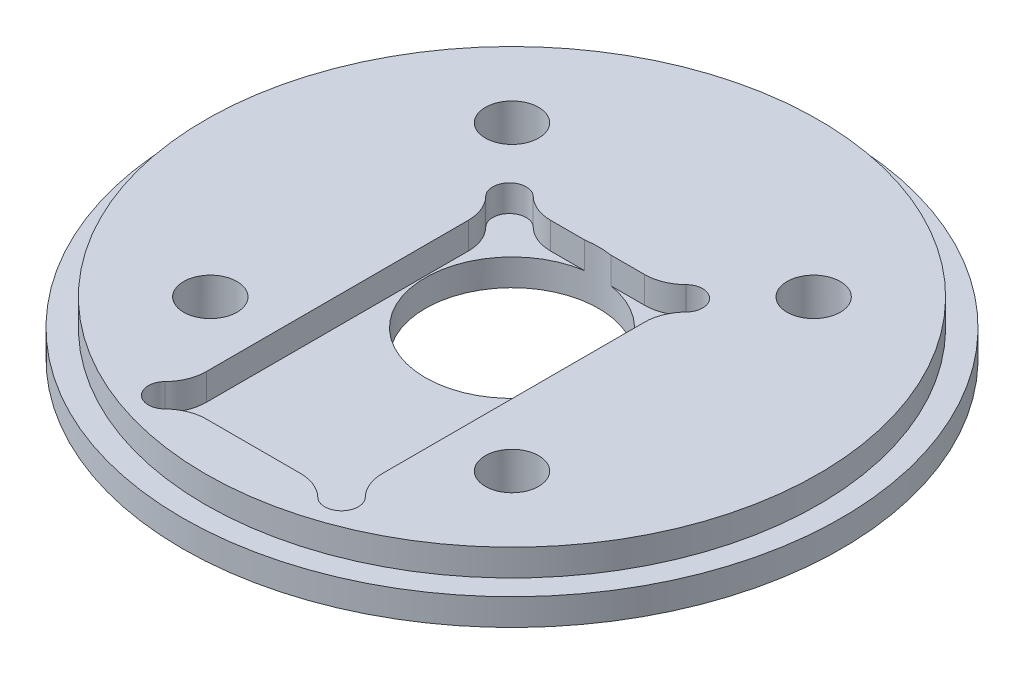
SolidWorks part; units mm, degrees
ref_plane "Front Plane" through (0, 0, 0) normal (0, 0, 1) x (1, 0, 0)
ref_plane "Top Plane" through (0, 0, 0) normal (0, 1, 0) x (1, 0, 0)
ref_plane "Right Plane" through (0, 0, 0) normal (1, 0, 0) x (0, 0, -1)
sketch "Sketch2" plane through (0, 0, 0) normal (0, 1, 0) x (1, 0, 0)
  circle A0 centre (0, 0) radius 39.243
  dimension "D1" = 78.486
extrude "Boss-Extrude1" add sketch "Sketch2" along normal blind 6.35
sketch "Sketch4" plane through (0, 6.35, 0) normal (0, 1, 0) x (1, 0, 0)
  circle A0 centre (0, 0) radius 36.5125
  circle A1 centre (0, 0) radius 39.243 construction
  circle A2 centre (0, 0) radius 39.243
  dimension "D1" = 73.025
extrude "Cut-Extrude1" cut sketch "Sketch4" against normal blind 3.175
sketch "Sketch5" plane through (0, 6.35, 0) normal (0, 1, 0) x (1, 0, 0)
  line L0 (17.9605, 17.9605) -> (-17.9605, -17.9605) construction
  line L1 (-17.9605, 17.9605) -> (17.9605, -17.9605) construction
  line L2 (-1000, 0) -> (49000, 0) construction
  point P1 (-17.9605, -17.9605)
  point P2 (17.9605, 17.9605)
  point P5 (17.9605, -17.9605)
  point P6 (-17.9605, 17.9605)
  dimension "D1" = 50.8
  dimension "D2" = 45
hole_wizard "1/4 (0.25) Diameter Hole1" positions "Sketch5" profile "Sketch6" hole size "1/4" standard "ANSI Inch" end condition through all
sketch "Sketch6" plane through (-17.9605, 6.35, -17.9605) normal (1, 0, 0) x (0, 0, 1)
  line L0 (0, 0) -> (0, 6.35)
  line L1 (0, 6.35) -> (3.175, 6.35)
  line L2 (3.175, 6.35) -> (3.175, 0)
  line L5 (3.175, 0) -> (0, 0)
  line L11 (0, -6.35) -> (0, 107.95) construction
  dimension "Thru Hole Dia." = 6.35
  dimension "Thru Hole Depth" = 6.35
sketch "Sketch7" plane through (0, 6.35, 0) normal (0, 1, 0) x (1, 0, 0)
  point P0 (0, 0)
hole_wizard "13/16 (0.8125) Diameter Hole1" positions "Sketch7" profile "Sketch8" hole size "13/16" standard "ANSI Inch" end condition through all
sketch "Sketch8" plane through (0, 6.35, 0) normal (1, 0, 0) x (0, 0, 1)
  line L0 (0, 0) -> (0, 6.35)
  line L1 (0, 6.35) -> (10.3187, 6.35)
  line L2 (10.3187, 6.35) -> (10.3187, 0)
  line L5 (10.3187, 0) -> (0, 0)
  line L11 (0, -6.35) -> (0, 107.95) construction
  dimension "Thru Hole Dia." = 20.6375
  dimension "Thru Hole Depth" = 6.35
sketch "Sketch11" plane through (0, 6.35, 0) normal (0, 1, 0) x (1, 0, 0)
  line L0 (0, -3.4925) -> (0, 3.4925) construction
  line L1 (-5.601, 10.2) -> (5.601, 10.2)
  line L2 (-10.5, 5.301) -> (-10.5, -25.901)
  line L3 (-5.601, -30.8) -> (5.601, -30.8)
  line L4 (10.5, 5.301) -> (10.5, -25.901)
  line L5 (-10.5, 10.2) -> (10.5, -30.8) construction
  line L6 (-10.5, -30.8) -> (10.5, 10.2) construction
  line L7 (0, -10.3) -> (7.6415, -10.3) construction
  line L8 (-10.5, -30.8) -> (-8.5, -30.8) construction
  line L9 (-10.5, -28.8) -> (-10.5, -30.8) construction
  line L10 (-10.5, 10.2) -> (-8.5, 10.2) construction
  line L11 (-10.5, 10.2) -> (-10.5, 8.2) construction
  line L12 (8.5, -30.8) -> (10.5, -30.8) construction
  line L13 (10.5, -28.8) -> (10.5, -30.8) construction
  line L14 (8.5, 10.2) -> (10.5, 10.2) construction
  line L15 (10.5, 10.2) -> (10.5, 8.2) construction
  arc A0 (-11.9286, -29.4003) -> (-9.1003, -32.2286) centre (-10.5, -30.8) ccw
  arc A1 (11.9286, -29.4003) -> (9.1003, -32.2286) centre (10.5, -30.8) cw
  arc A2 (11.9286, 8.8003) -> (9.1003, 11.6286) centre (10.5, 10.2) ccw
  arc A3 (-11.9286, 8.8003) -> (-9.1003, 11.6286) centre (-10.5, 10.2) cw
  arc A4 (-11.9286, -29.4003) -> (-10.5, -25.901) centre (-15.5, -25.901) ccw
  arc A5 (-9.1003, -32.2286) -> (-5.601, -30.8) centre (-5.601, -35.8) cw
  arc A6 (11.9286, -29.4003) -> (10.5, -25.901) centre (15.5, -25.901) cw
  arc A7 (9.1003, -32.2286) -> (5.601, -30.8) centre (5.601, -35.8) ccw
  arc A8 (11.9286, 8.8003) -> (10.5, 5.301) centre (15.5, 5.301) ccw
  arc A9 (9.1003, 11.6286) -> (5.601, 10.2) centre (5.601, 15.2) cw
  arc A10 (-9.1003, 11.6286) -> (-5.601, 10.2) centre (-5.601, 15.2) ccw
  arc A11 (-11.9286, 8.8003) -> (-10.5, 5.301) centre (-15.5, 5.301) cw
  point P0 (0, 0)
  point P1 (0, -10.3)
  point P19 (-29.6088, -9.3532)
  point P20 (7.6415, -10.3)
  dimension "D4" = 2
  dimension "D5" = 5
  dimension "D1" = 10.2
  dimension "D2" = 21
  dimension "D3" = 41
extrude "Cut-Extrude3" cut sketch "Sketch11" against normal blind 3.175
sketch "Sketch9" plane through (0, 0, 0) normal (0, -1, 0) x (1, 0, 0)
  circle A0 centre (-17.9605, -17.9605) radius 3.175 construction
  circle A1 centre (17.9605, -17.9605) radius 3.175 construction
  circle A2 centre (17.9605, 17.9605) radius 3.175 construction
  circle A3 centre (-17.9605, 17.9605) radius 3.175 construction
  circle A4 centre (-17.9605, -17.9605) radius 3.175 construction
  circle A5 centre (17.9605, -17.9605) radius 3.175 construction
  circle A6 centre (17.9605, 17.9605) radius 3.175 construction
  circle A7 centre (-17.9605, 17.9605) radius 3.175 construction
  circle A8 centre (-17.9605, 17.9605) radius 6.0325
  circle A9 centre (17.9605, 17.9605) radius 6.0325
  circle A10 centre (17.9605, -17.9605) radius 6.0325
  circle A11 centre (-17.9605, -17.9605) radius 6.0325
  point P13 (-17.9605, 17.9605)
  point P14 (17.9605, 17.9605)
  point P15 (17.9605, -17.9605)
  point P16 (-17.9605, -17.9605)
  dimension "D1" = 12.065
extrude "Cut-Extrude2" cut sketch "Sketch9" against normal blind 1.5875
equation "\"AIRFRAME_OD\"= 3.142in"
equation "\"AIRFRAME_ID\"= 3.00in"
equation "\"FLAT_T\"= 0.125in"
equation "\"NOSE_EXP_L\"= 3.5in"
equation "\"NOSE_SHOULDER_L\"= 1.5in"
equation "\"MAIN_L\"= 30in"
equation "\"RECO_COUP_L\"= 6in"
equation "\"RECO_SWITCH_L\"= 1.5in"
equation "\"DROGUE_L\"= 14in"
equation "\"ATS_FORE_COUP_L\"= 4in"
equation "\"ATS_AFT_COUP_L\"= 2.5in"
equation "\"LOWER_L\"= 16in"
equation "\"FIN_N\"= 4"
equation "\"CR_AFT_X\"= 0.5in"
equation "\"CR_FORE_X\"= 6in"
equation "\"D1@Boss-Extrude1\"=2*\"FLAT_T\""
equation "\"COUPLER_OD\"= 2.998in"
equation "\"COUPLER_ID\"= 2.875in"
equation "\"RECO_ROD_X\"= 1.5in"
equation "\"ATS_ROD_X\"= 2in"
equation "\"FIN_ROOT\"= 5in"
equation "\"FIN_X\"= 0.75in"
equation "\"MOTOR_OD\"= 2.25in"
equation "\"MOTOR_ID\"= 2.126in"
equation "\"MOTOR_L\"= 8in"
equation "\"MOTOR_LOWER_X\"= 0.5in"
equation "\"D1@Sketch4\"=\"COUPLER_ID\""
equation "\"D1@Cut-Extrude1\"=\"FLAT_T\""
equation "\"D1@Cut-Extrude3\"=\"FLAT_T\""
